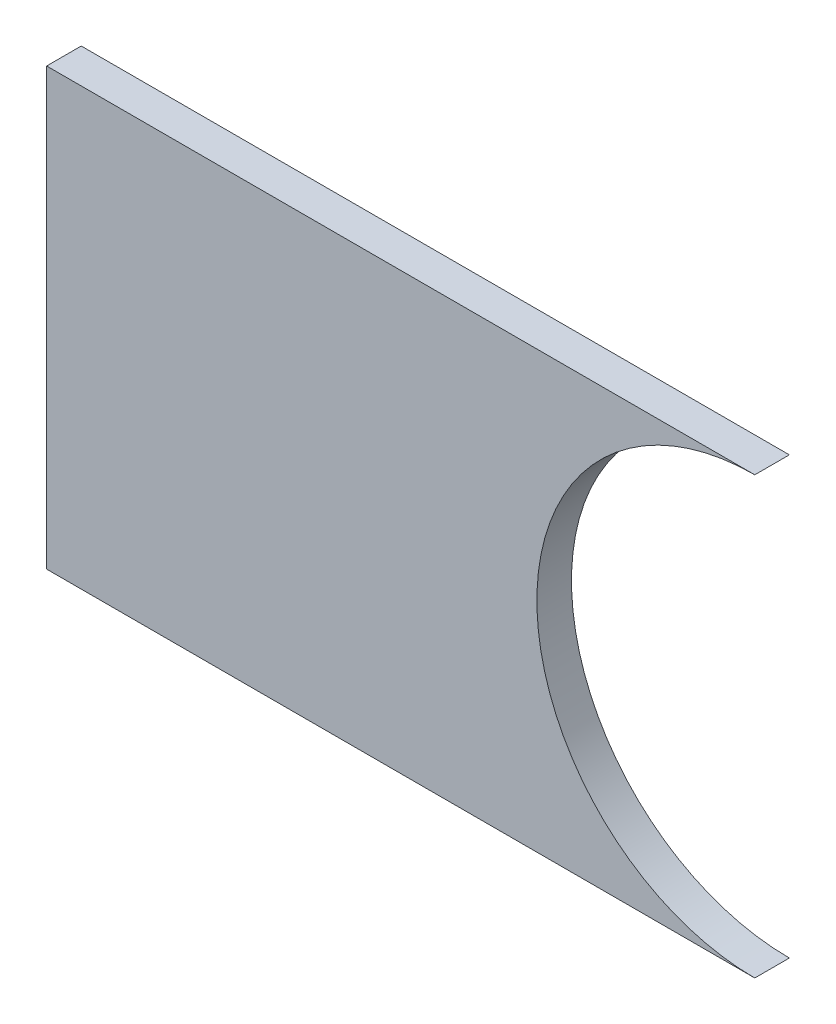
SolidWorks part; units mm, degrees
material "Acrylic (Medium-high impact)"
ref_plane "Front Plane" through (0, 0, 0) normal (0, 0, 1) x (1, 0, 0)
ref_plane "Top Plane" through (0, 0, 0) normal (0, 1, 0) x (1, 0, 0)
ref_plane "Right Plane" through (0, 0, 0) normal (1, 0, 0) x (0, 0, -1)
sketch "Sketch1" plane through (0, 0, 0) normal (0, 0, 1) x (1, 0, 0)
  line L0 (0, 0) -> (65, 0)
  line L1 (0, 0) -> (0, 40)
  line L2 (0, 40) -> (65, 40)
  arc A0 (65, 40) -> (65, 0) centre (65, 20) ccw
  point P8 (45, 20)
  dimension "D1" = 20
  dimension "D2" = 45
extrude "Boss-Extrude1" add sketch "Sketch1" along normal blind 3.175
